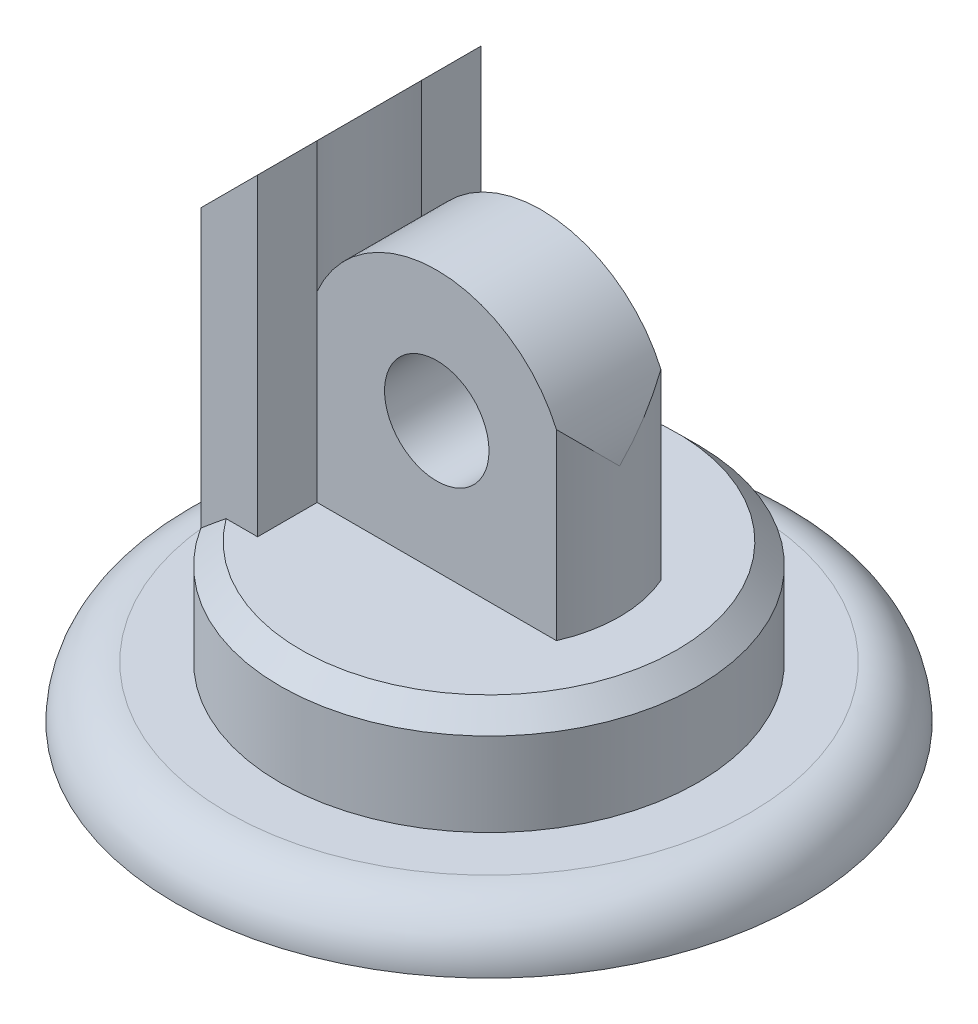
SolidWorks part; units mm, degrees
ref_plane "Front Plane" through (0, 0, 0) normal (0, 0, 1) x (1, 0, 0)
ref_plane "Top Plane" through (0, 0, 0) normal (0, 1, 0) x (1, 0, 0)
ref_plane "Right Plane" through (0, 0, 0) normal (1, 0, 0) x (0, 0, -1)
sketch "Sketch1" plane through (0, 0, 0) normal (0, 0, 1) x (1, 0, 0)
  line L1 (-25, 25) -> (25, 25)
  line L2 (-25, 25) -> (-25, -25)
  line L3 (-25, -25) -> (25, -25)
  line L4 (25, 25) -> (25, -25)
  line L5 (-25, 25) -> (25, -25) construction
  line L6 (-25, -25) -> (25, 25) construction
  point P0 (0, 0)
  dimension "D1" = 50
  dimension "D2" = 50
extrude "Boss-Extrude1" add sketch "Sketch1" along normal blind 10 and the other way blind 10
sketch "Sketch3" plane through (0, 25, 0) normal (0, 1, 0) x (1, 0, 0)
  circle A0 centre (0, 0) radius 25
  line M2 (-25, 10) -> (-25, -10)
  line M3 (-25, -10) -> (25, -10)
  line M4 (25, -10) -> (25, 10)
  line M5 (25, 10) -> (-25, 10)
extrude "Cut-Extrude1" cut sketch "Sketch3" against normal through all contours A0 M5 M2 | A0 M2 M3 | A0 M3 M4 | A0 M4 M5 region at (24.3786, 25, 7.5213) region at (24.3786, 25, -7.5213) region at (-24.3786, 25, -7.5213) region at (-24.3786, 25, 7.5213)
sketch "Sketch4" plane through (0, 0, -10) normal (0, 0, -1) x (-1, 0, 0)
  line L0 (-25, 0) -> (-25, 25)
  line L1 (-25, 25) -> (0, 25)
  line L2 (0, 25) -> (25, 25)
  line L3 (25, 25) -> (25, 0)
  circle A0 centre (0, 0) radius 25
  line M1 (22.9129, -25) -> (22.9129, 25)
  line M2 (22.9129, 25) -> (-22.9129, 25)
  line M3 (-22.9129, 25) -> (-22.9129, -25)
extrude "Cut-Extrude3" cut sketch "Sketch4" against normal through all contours A0 L1 L0 M3 | A0 M2 M3 | A0 M1 M2 | A0 L3 L2 M1 region at (24.0321, 15.7115, -10) region at (17.5813, 20.8879, -10) region at (-17.5813, 20.8879, -10) region at (-24.0321, 15.7115, -10)
sketch "Sketch5" plane through (0, -25, 0) normal (0, -1, 0) x (1, 0, 0)
  circle A0 centre (0, 0) radius 40
extrude "Boss-Extrude2" add sketch "Sketch5" along normal blind 20 contours A0
sketch "Sketch6" plane through (0, -45, 0) normal (0, -1, 0) x (1, 0, 0)
  circle A0 centre (0, 0) radius 60
extrude "Boss-Extrude3" add sketch "Sketch6" along normal blind 10
sketch "Sketch7" plane through (0, -55, 0) normal (0, -1, 0) x (-1, 0, 0)
  circle A0 centre (0, 0) radius 10
extrude "Boss-Extrude4" add sketch "Sketch7" along normal blind 20
sketch "Sketch9" plane through (0, 0, 10) normal (0, 0, 1) x (1, 0, 0)
  circle A0 centre (0, 0) radius 10
extrude "Cut-Extrude4" cut sketch "Sketch9" against normal through all
sketch "Sketch13" plane through (0, -25, 0) normal (0, 1, 0) x (1, 0, 0)
  line L0 (-22.9129, 10) -> (-22.9129, -10) construction
  line L1 (-22.9129, -10) -> (22.9129, -10) construction
  line L2 (-22.9129, 10) -> (-22.9129, 21.3936)
  line L3 (-22.9129, -10) -> (-22.9129, -21.3936)
  line L4 (-22.9129, -21.3936) -> (-33.7981, -21.3936)
  line L5 (-22.9129, 21.3936) -> (-33.7981, 21.3936)
  arc A0 (-22.9129, 10) -> (-22.9129, -10) centre (0, 0) ccw
  arc A1 (-33.7981, 21.3936) -> (-33.7981, -21.3936) centre (0, 0) ccw
extrude "Boss-Extrude8" add sketch "Sketch13" along normal blind 60
sketch "Sketch14" plane through (0, 0, 21.3936) normal (0, 0, 1) x (1, 0, 0)
  line L0 (-22.9129, 35) -> (-44.2659, 13.647)
  line L1 (-44.2659, 13.647) -> (-44.2659, 44.1807)
  line L2 (-44.2659, 44.1807) -> (-22.9129, 35)
extrude "Cut-Extrude5" cut sketch "Sketch14" against normal through all
fillet "Fillet1" radius 10 1 edges at (0, -45, -60)
chamfer "Chamfer1" distance 4 angle 45 1 edges at (40, -25, 0)
